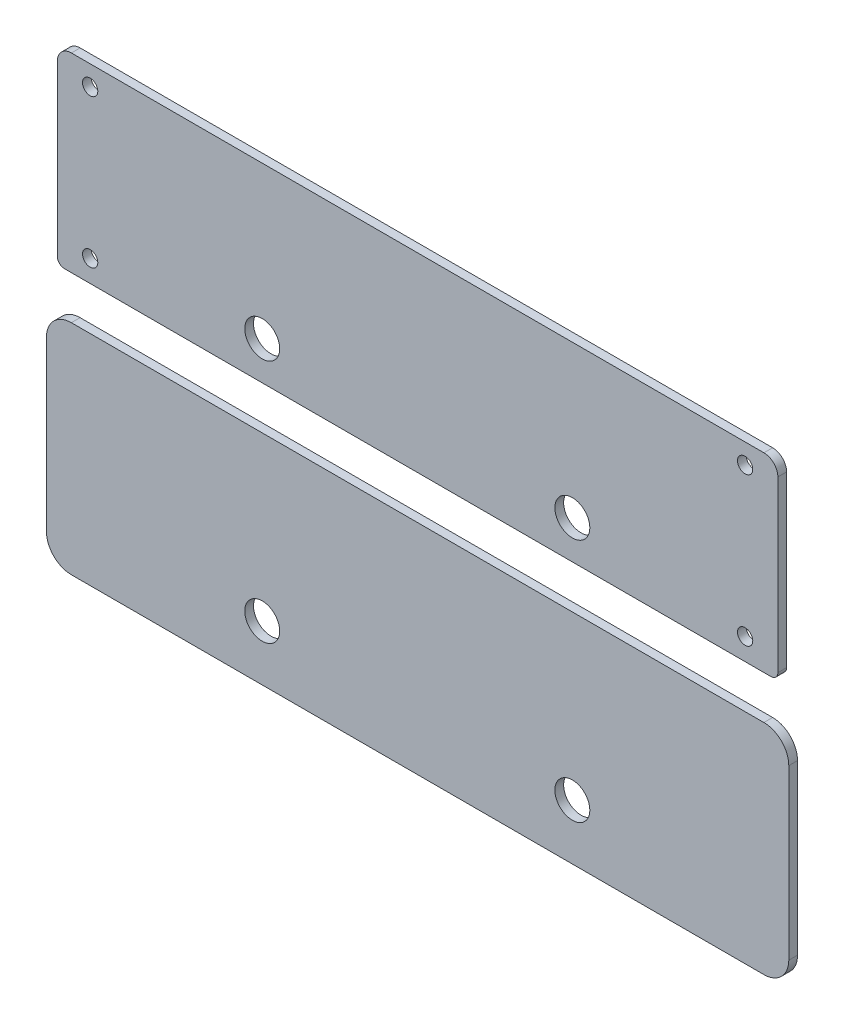
SolidWorks part; units mm, degrees
ref_plane "Front" through (0, 0, 0) normal (0, 0, 1) x (1, 0, 0)
ref_plane "Top" through (0, 0, 0) normal (0, 1, 0) x (1, 0, 0)
ref_plane "Right" through (0, 0, 0) normal (1, 0, 0) x (0, 0, -1)
sketch "Sketch1" plane through (0, 0, 0) normal (0, 0, 1) x (1, 0, 0)
  line L0 (-52.6295, -31.75) -> (-37.7705, -31.75)
  line L1 (37.5705, -31.75) -> (52.4295, -31.75)
  line L2 (-107.95, 24.511) -> (-107.95, -24.511)
  line L3 (-100.711, -31.75) -> (-52.6295, -31.75)
  line L4 (-37.7705, -31.75) -> (37.5705, -31.75)
  line L5 (52.4295, -31.75) -> (100.711, -31.75)
  line L6 (107.95, -24.511) -> (107.95, 24.511)
  line L7 (100.711, 31.75) -> (-100.711, 31.75)
  line L24 (100.711, 99.695) -> (-100.711, 99.695)
  line L25 (-104.775, 95.631) -> (-104.775, 50.345)
  line L31 (104.775, 50.345) -> (104.775, 95.631)
  line L32 (107.95, 46.609) -> (107.95, 95.631) [skipped]
  line L33 (84.775, 44.345) -> (-84.775, 44.345)
  line L34 (100.711, 102.87) -> (-100.711, 102.87) [skipped]
  line L35 (84.775, 44.345) -> (84.775, 50.345)
  line L36 (52.4295, 39.37) -> (100.711, 39.37) [skipped]
  line L37 (84.775, 50.345) -> (104.775, 50.345)
  line L38 (37.5705, 39.37) -> (52.4295, 39.37) [skipped]
  line L40 (-37.7705, 39.37) -> (37.5705, 39.37) [skipped]
  line L41 (0, 99.695) -> (0, 44.345) construction
  line L42 (-52.6295, 39.37) -> (-37.7705, 39.37) [skipped]
  line L43 (-84.775, 50.345) -> (-104.775, 50.345)
  line L44 (-100.711, 39.37) -> (-52.6295, 39.37) [skipped]
  line L45 (-84.775, 44.345) -> (-84.775, 50.345)
  line L46 (-107.95, 95.631) -> (-107.95, 46.609) [skipped]
  circle A0 centre (-45.2, -15.6502) radius 5.08
  circle A1 centre (45, -15.6502) radius 5.08
  arc A2 (-100.711, 31.75) -> (-107.95, 24.511) centre (-100.711, 24.511) ccw
  arc A3 (-107.95, -24.511) -> (-100.711, -31.75) centre (-100.711, -24.511) ccw
  arc A4 (100.711, -31.75) -> (107.95, -24.511) centre (100.711, -24.511) ccw
  arc A5 (107.95, 24.511) -> (100.711, 31.75) centre (100.711, 24.511) ccw
  circle A10 centre (-45.2, 55.4698) radius 5.08
  circle A11 centre (45, 55.4698) radius 5.08
  arc A18 (-100.711, 99.695) -> (-104.775, 95.631) centre (-100.711, 95.631) ccw
  arc A21 (104.775, 95.631) -> (100.711, 99.695) centre (100.711, 95.631) ccw
  arc A24 (107.95, 95.631) -> (100.711, 102.87) centre (100.711, 95.631) ccw [skipped]
  circle A25 centre (66.273, 2.3) radius 1.905 construction
  arc A26 (100.711, 39.37) -> (107.95, 46.609) centre (100.711, 46.609) ccw [skipped]
  arc A28 (-107.95, 46.609) -> (-100.711, 39.37) centre (-100.711, 46.609) ccw [skipped]
  circle A29 centre (35.023, 2.3) radius 1.905 construction
  arc A30 (-100.711, 102.87) -> (-107.95, 95.631) centre (-100.711, 95.631) ccw [skipped]
  circle A32 centre (50.648, 2.3) radius 12.065 construction
  circle A34 centre (12.5, 2.3) radius 9.25 construction
  dimension "D3" = 2
extrude "Boss-Extrude1" add sketch "Sketch1" along normal blind 2.54
sketch "Sketch2" [suppressed] plane through (0, 0, 2.54) normal (0, 0, 1) x (1, 0, 0)
  line L0 (-20.0864, 22.2366) -> (3.9841, 22.2366)
  line L1 (3.9841, 22.2366) -> (3.9841, 4.3544)
  line L2 (3.9841, 4.3544) -> (21.8236, 4.3544)
  line L3 (21.8236, 4.3544) -> (21.8236, -19.7588)
  line L4 (21.8236, -19.7588) -> (15.806, -19.7588)
  line L5 (15.806, -19.7588) -> (15.806, -1.7486)
  line L6 (15.806, -1.7486) -> (-1.9908, -1.7486)
  line L7 (-1.9908, -1.7486) -> (-1.9908, 16.2189)
  line L8 (-1.9908, 16.2189) -> (-20.0864, 16.2189)
  line L9 (-20.0864, 16.2189) -> (-20.0864, 22.2366)
  line L10 (-20.0864, 4.3544) -> (-14.0261, 4.3544)
  line L11 (-14.0261, 4.3544) -> (-14.0261, -13.6985)
  line L12 (-14.0261, -13.6985) -> (3.9841, -13.6985)
  line L13 (3.9841, -13.6985) -> (3.9841, -19.7588)
  line L14 (3.9841, -19.7588) -> (-20.0864, -19.7588)
  line L15 (-20.0864, -19.7588) -> (-20.0864, 4.3544)
extrude "Cut-Extrude1" [suppressed] cut sketch "Sketch2" against normal through all
sketch "Sketch3" [suppressed] plane through (0, 0, 2.54) normal (0, 0, 1) x (1, 0, 0)
  circle A0 centre (-45.2, 55.4698) radius 5.08 construction
  circle A1 centre (-45.2, 55.4698) radius 5.08
  circle A2 centre (45, 55.4698) radius 5.08 construction
  circle A3 centre (45, 55.4698) radius 5.08
extrude "Boss-Extrude2" [suppressed] add sketch "Sketch3" against normal through all
sketch "Sketch5" [suppressed] plane through (0, 0, 2.54) normal (0, 0, 1) x (1, 0, 0)
  line L0 (3.9841, -19.7588) -> (3.9841, -13.6985) construction
  line L1 (-20.0864, -19.7588) -> (3.9841, -19.7588) construction
  line L2 (-20.0864, 4.3544) -> (-20.0864, -19.7588) construction
  line L3 (-14.0261, 4.3544) -> (-20.0864, 4.3544) construction
  line L4 (-14.0261, -13.6985) -> (-14.0261, 4.3544) construction
  line L5 (3.9841, -13.6985) -> (-14.0261, -13.6985) construction
  line L6 (3.9841, -19.7588) -> (3.9841, -13.6985)
  line L7 (-20.0864, -19.7588) -> (3.9841, -19.7588)
  line L8 (-20.0864, 4.3544) -> (-20.0864, -19.7588)
  line L9 (-14.0261, 4.3544) -> (-20.0864, 4.3544)
  line L10 (-14.0261, -13.6985) -> (-14.0261, 4.3544)
  line L11 (3.9841, -13.6985) -> (-14.0261, -13.6985)
  line L12 (-1.9908, -1.7486) -> (15.806, -1.7486) construction
  line L13 (-1.9908, 16.2189) -> (-1.9908, -1.7486) construction
  line L14 (-20.0864, 16.2189) -> (-1.9908, 16.2189) construction
  line L15 (-20.0864, 22.2366) -> (-20.0864, 16.2189) construction
  line L16 (3.9841, 22.2366) -> (-20.0864, 22.2366) construction
  line L17 (3.9841, 4.3544) -> (3.9841, 22.2366) construction
  line L18 (21.8236, 4.3544) -> (3.9841, 4.3544) construction
  line L19 (21.8236, -19.7588) -> (21.8236, 4.3544) construction
  line L20 (15.806, -19.7588) -> (21.8236, -19.7588) construction
  line L21 (15.806, -1.7486) -> (15.806, -19.7588) construction
  line L22 (-1.9908, -1.7486) -> (15.806, -1.7486)
  line L23 (-1.9908, 16.2189) -> (-1.9908, -1.7486)
  line L24 (-20.0864, 16.2189) -> (-1.9908, 16.2189)
  line L25 (-20.0864, 22.2366) -> (-20.0864, 16.2189)
  line L26 (3.9841, 22.2366) -> (-20.0864, 22.2366)
  line L27 (3.9841, 4.3544) -> (3.9841, 22.2366)
  line L28 (21.8236, 4.3544) -> (3.9841, 4.3544)
  line L29 (21.8236, -19.7588) -> (21.8236, 4.3544)
  line L30 (15.806, -19.7588) -> (21.8236, -19.7588)
  line L31 (15.806, -1.7486) -> (15.806, -19.7588)
  circle A0 centre (-45.2, -15.6502) radius 5.08 construction
  circle A1 centre (-45.2, -15.6502) radius 5.08
  circle A2 centre (45, -15.6502) radius 5.08 construction
  circle A3 centre (45, -15.6502) radius 5.08
extrude "Boss-Extrude3" [suppressed] add sketch "Sketch5" against normal through all
sketch "Sketch6" [suppressed] plane through (0, 0, 2.54) normal (0, 0, 1) x (1, 0, 0)
  circle A0 centre (12.5, 2.3) radius 9.25 construction
  circle A1 centre (12.5, 2.3) radius 9.25
  circle A2 centre (35.023, 2.3) radius 1.905 construction
  circle A3 centre (35.023, 2.3) radius 1.905
  circle A4 centre (50.648, 2.3) radius 12.065 construction
  circle A5 centre (50.648, 2.3) radius 12.065
  circle A6 centre (66.273, 2.3) radius 1.905 construction
  circle A7 centre (66.273, 2.3) radius 1.905
extrude "Cut-Extrude2" [suppressed] cut sketch "Sketch6" against normal through all
sketch "Sketch7" [suppressed] plane through (0, 0, 0) normal (0, 0, -1) x (-1, 0, 0)
  line L1 (-74.2733, 90.9286) -> (5.6813, 90.9286)
  line L2 (-74.2733, 90.9286) -> (-74.2733, 56.2734)
  line L3 (-74.2733, 56.2734) -> (5.6813, 56.2734)
  line L4 (5.6813, 90.9286) -> (5.6813, 56.2734)
extrude "Cut-Extrude3" [suppressed] cut sketch "Sketch7" against normal through all
sketch "Sketch8" [suppressed] plane through (0, 0, 2.54) normal (0, 0, 1) x (1, 0, 0)
  line L0 (0, 31.75) -> (0, 1.16) construction
  line L1 (95.25, -20.43) -> (-95.25, -20.43) construction
  line L2 (95.25, -20.43) -> (95.25, 22.75) construction
  line L3 (95.25, 22.75) -> (-95.25, 22.75) construction
  line L4 (-95.25, -20.43) -> (-95.25, 22.75) construction
  line L5 (95.25, -20.43) -> (-95.25, 22.75) construction
  line L6 (95.25, 22.75) -> (-95.25, -20.43) construction
  line L7 (100.711, 31.75) -> (-100.711, 31.75) construction
  circle A0 centre (-95.25, 22.75) radius 2.2225
  circle A1 centre (-95.25, -20.43) radius 2.2225
  circle A2 centre (95.25, -20.43) radius 2.2225
  circle A3 centre (95.25, 22.75) radius 2.2225
  dimension "D1" = 4.445
  dimension "D2" = 43.18
  dimension "D3" = 190.5
  dimension "D4" = 9
extrude "Cut-Extrude4" [suppressed] cut sketch "Sketch8" against normal through all
sketch "Sketch9" plane through (0, 0, 2.54) normal (0, 0, 1) x (1, 0, 0)
  line L0 (-104.775, 50.345) -> (-84.775, 50.345)
  line L1 (-84.775, 50.345) -> (-84.775, 44.345)
  line L2 (-84.775, 44.345) -> (-104.775, 44.345)
  line L3 (-104.775, 44.345) -> (-104.775, 50.345)
  line L4 (84.775, 50.345) -> (104.775, 50.345)
  line L5 (104.775, 50.345) -> (104.775, 44.345)
  line L6 (104.775, 44.345) -> (84.775, 44.345)
  line L7 (84.775, 50.345) -> (84.775, 44.345)
extrude "Boss-Extrude4" add sketch "Sketch9" against normal up to surface (2.54 mm away) up to face at (0, 68.2405, 0)
fillet "Fillet1" radius 2 2 edges at (104.775, 44.345, 1.27) (-104.775, 44.345, 1.27)
sketch "Sketch10" plane through (0, 0, 2.54) normal (0, 0, 1) x (1, 0, 0)
  circle A1 centre (95.25, 93.87) radius 2.2225
  circle A2 centre (95.25, 93.87) radius 2.2225
  circle A3 centre (95.25, 50.69) radius 2.2225
  circle A4 centre (95.25, 50.69) radius 2.2225
  circle A5 centre (-95.25, 50.69) radius 2.2225
  circle A6 centre (-95.25, 50.69) radius 2.2225
  circle A7 centre (-95.25, 93.87) radius 2.2225
  circle A8 centre (-95.25, 93.87) radius 2.2225
  dimension "D1" = 0
  dimension "D2" = 0
  dimension "D3" = 0
  dimension "D4" = 0
extrude "Cut-Extrude5" cut sketch "Sketch10" against normal through all
sketch "Sketch12" [suppressed] plane through (0, 0, 0) normal (0, 0, -1) x (-1, 0, 0)
  line L1 (104.775, 50.345) -> (84.775, 50.345)
  line L2 (104.775, 50.345) -> (104.775, 44.345)
  line L3 (104.775, 44.345) -> (84.775, 44.345)
  line L4 (84.775, 50.345) -> (84.775, 44.345)
  line L5 (-104.775, 50.345) -> (-84.775, 50.345)
  line L6 (-104.775, 50.345) -> (-104.775, 44.345)
  line L7 (-104.775, 44.345) -> (-84.775, 44.345)
  line L8 (-84.775, 50.345) -> (-84.775, 44.345)
extrude "Boss-Extrude5" [suppressed] add sketch "Sketch12" against normal up to surface (2.54 mm away) up to face at (-93.0275, 93.87, 2.54)
fillet "Fillet2" [suppressed] radius 2.5
sketch "Sketch11" [suppressed] plane through (0, 0, 2.54) normal (0, 0, 1) x (1, 0, 0)
  circle A1 centre (95.25, 93.87) radius 2.2225
  circle A2 centre (95.25, 93.87) radius 2.2225
  circle A3 centre (95.25, 50.69) radius 2.2225
  circle A4 centre (95.25, 50.69) radius 2.2225
  circle A5 centre (-95.25, 50.69) radius 2.2225
  circle A6 centre (-95.25, 50.69) radius 2.2225
  circle A7 centre (-95.25, 93.87) radius 2.2225
  circle A8 centre (-95.25, 93.87) radius 2.2225
  dimension "D1" = 0
  dimension "D2" = 0
  dimension "D3" = 0
  dimension "D4" = 0
extrude "Cut-Extrude6" [suppressed] cut sketch "Sketch11" against normal through all
sketch "Sketch13" [suppressed] plane through (0, 0, 2.54) normal (0, 0, 1) x (1, 0, 0)
  circle A1 centre (-95.25, 22.75) radius 2.2225
  circle A2 centre (-95.25, 22.75) radius 2.2225
  circle A3 centre (-95.25, -20.43) radius 2.2225
  circle A4 centre (-95.25, -20.43) radius 2.2225
  circle A5 centre (95.25, -20.43) radius 2.2225
  circle A6 centre (95.25, -20.43) radius 2.2225
  circle A7 centre (95.25, 22.75) radius 2.2225
  circle A8 centre (95.25, 22.75) radius 2.2225
  dimension "D1" = 0
  dimension "D2" = 0
  dimension "D3" = 0
  dimension "D4" = 0
extrude "Cut-Extrude7" [suppressed] cut sketch "Sketch13" against normal through all
